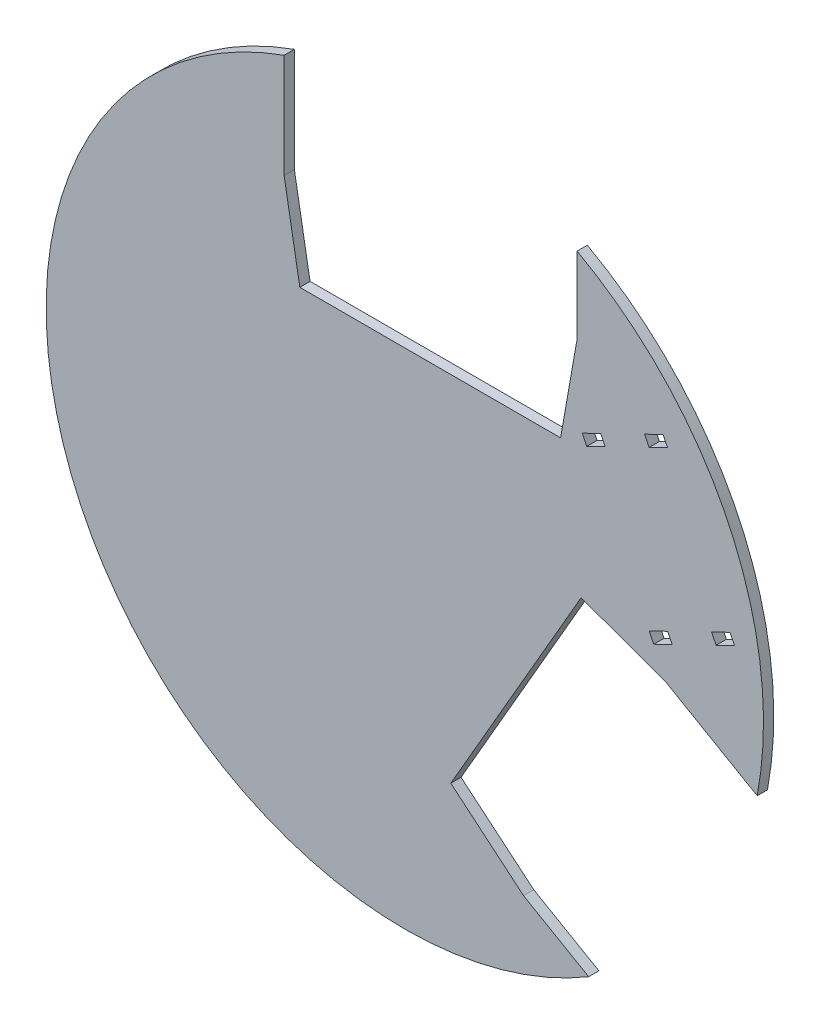
SolidWorks part; units mm, degrees
material "Balsa"
ref_plane "Plan de face" through (0, 0, 0) normal (0, 0, 1) x (1, 0, 0)
ref_plane "Plan de dessus" through (0, 0, 0) normal (0, 1, 0) x (1, 0, 0)
ref_plane "Plan de droite" through (0, 0, 0) normal (1, 0, 0) x (0, 0, -1)
sketch "Esquisse1" plane through (0, 0, 0) normal (0, 0, 1) x (1, 0, 0)
  circle A0 centre (0.6471, 0.3143) radius 175
  dimension "D1" = 350
extrude "Boss.-Extru.1" add sketch "Esquisse1" along normal blind 5
sketch "Esquisse2" plane through (0, 0, 0) normal (0, 0, -1) x (-1, 0, 0)
  line L0 (58.2408, 114.332) -> (58.2408, 213.8766)
  line L1 (58.2408, 213.8766) -> (-84.6817, 213.8766)
  line L2 (-84.6817, 213.8766) -> (-84.6817, 116.5135)
  line L3 (0, 0) -> (-290.6498, 0) construction
  line L4 (-84.6817, 116.5135) -> (-76.6366, 70.8876)
  line L5 (-76.6366, 70.8876) -> (50.5804, 70.8876)
  line L6 (50.5804, 70.8876) -> (58.2408, 114.332)
  line L7 (-128.1349, -6.728) -> (-214.343, -56.5003)
  line L8 (-214.343, -56.5003) -> (-142.8818, -180.2748)
  line L9 (-142.8818, -180.2748) -> (-58.5628, -131.5932)
  line L10 (-58.5628, -131.5932) -> (-23.0722, -101.8131)
  line L11 (-23.0722, -101.8131) -> (-86.6807, 8.3601)
  line L12 (-86.6807, 8.3601) -> (-128.1349, -6.728)
  point P16 (0, 0)
  point P43 (0, 0)
  dimension "D5" = 142.989
  dimension "D6" = 99.5446
  dimension "D1" = 127.217
  dimension "D2" = 100
  dimension "D3" = 100
  dimension "D4" = 142.9225
  dimension "D7" = 70.8876
  dimension "D8" = 50.5804
extrude "Enlèv. mat.-Extru.1" cut sketch "Esquisse2" against normal blind 5
sketch "Esquisse3" plane through (0, 0, 5) normal (0, 0, 1) x (1, 0, 0)
  line L0 (0, 0) -> (0, 103.8673) construction
  line L16 (0, 0) -> (104.6701, 42.2895) construction
  line B0 (122.0981, 6.4136) -> (119.9134, 10.911)
  line B1 (128.9082, 15.2806) -> (119.9134, 10.911)
  line B2 (131.093, 10.7832) -> (122.0981, 6.4136)
  line B3 (131.093, 10.7832) -> (128.9082, 15.2806)
  line B4 (159.3288, 30.0585) -> (150.334, 25.689)
  line B5 (152.5188, 21.1916) -> (150.334, 25.689)
  line B6 (161.5136, 25.5611) -> (159.3288, 30.0585)
  line B7 (161.5136, 25.5611) -> (152.5188, 21.1916)
  line B8 (126.6575, 97.3129) -> (117.6627, 92.9433)
  line B9 (126.6575, 97.3129) -> (128.8423, 92.8154)
  line B10 (117.6627, 92.9433) -> (119.8475, 88.4459)
  line B11 (128.8423, 92.8154) -> (119.8475, 88.4459)
  line B12 (96.2369, 82.5349) -> (98.4217, 78.0375)
  line B13 (96.2369, 82.5349) -> (87.2421, 78.1653)
  line B14 (98.4217, 78.0375) -> (89.4269, 73.6679)
  line B15 (87.2421, 78.1653) -> (89.4269, 73.6679)
  line B16 (87.2421, 78.1653) -> (104.6701, 42.2895) construction
  dimension "D1" = 112.6276
  dimension "D2" = 68
sketch_block_instance "Bloc1-1"
sketch_block "Bloc1" parameters "D1"=5, "D2"=23.8202, "D3"=39.885, "D4"=10
extrude "Enlèv. mat.-Extru.2" cut sketch "Esquisse3" against normal blind 10
